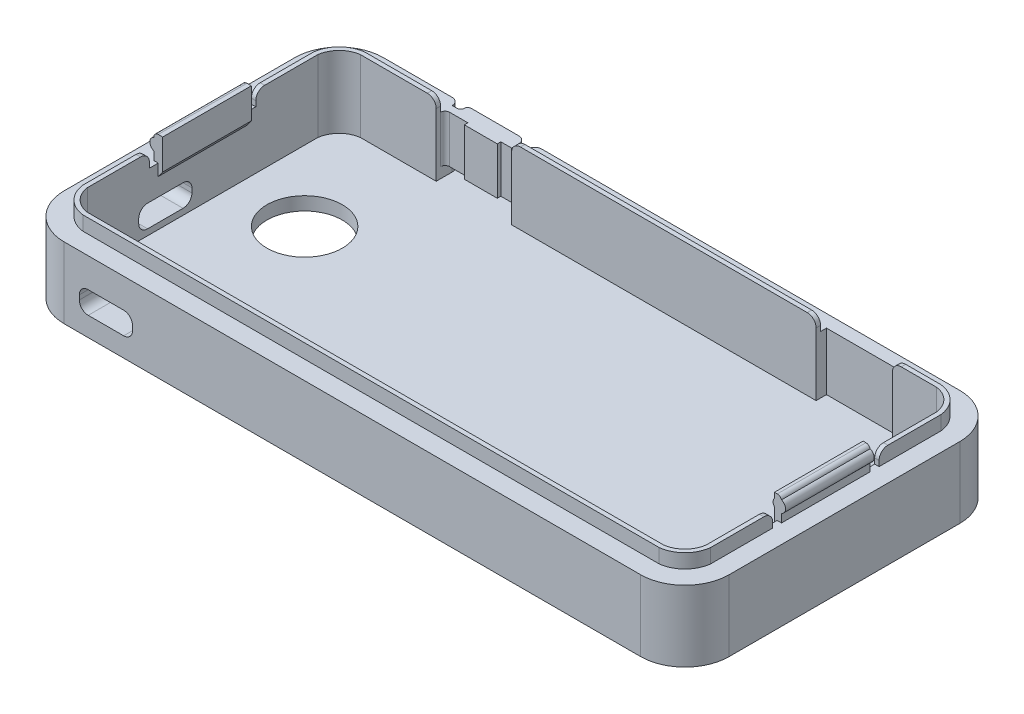
SolidWorks part; units mm, degrees
ref_plane "前视基准面" through (0, 0, 0) normal (0, 0, 1) x (1, 0, 0)
ref_plane "上视基准面" through (0, 0, 0) normal (0, 1, 0) x (1, 0, 0)
ref_plane "右视基准面" through (0, 0, 0) normal (1, 0, 0) x (0, 0, -1)
sketch "zero" plane through (0, 0, 0) normal (0, 1, 0) x (1, 0, 0)
  line L1 (-29.5, 15) -> (29.5, 15)
  line L2 (-32.5, 12) -> (-32.5, -12)
  line L3 (-29.5, -15) -> (29.5, -15)
  line L4 (32.5, 12) -> (32.5, -12)
  line L5 (-32.5, 15) -> (32.5, -15) construction
  line L6 (-32.5, -15) -> (32.5, 15) construction
  line L7 (-25.7, -15) -> (-14.5, -15)
  line L8 (-25.7, -15) -> (-25.7, -9.6569)
  line L9 (-25.7, -9.6569) -> (-14.5, -9.6569)
  line L10 (-14.5, -15) -> (-14.5, -9.6569)
  line L11 (5.2, -15) -> (12.7, -15)
  line L12 (5.2, -15) -> (5.2, -11)
  line L13 (5.2, -11) -> (12.7, -11)
  line L14 (12.7, -15) -> (12.7, -11)
  line L15 (17.8, -15) -> (25.3, -15)
  line L16 (17.8, -15) -> (17.8, -11)
  line L17 (17.8, -11) -> (25.3, -11)
  line L18 (25.3, -15) -> (25.3, -11)
  line L19 (-32.5, 7.7) -> (-19.5, 7.7)
  line L20 (-32.5, 7.7) -> (-32.5, -4.3)
  line L21 (-32.5, -4.3) -> (-19.5, -4.3)
  line L22 (-19.5, 7.7) -> (-19.5, -4.3)
  line L23 (-25.5, 14) -> (25.5, 14)
  line L24 (-25.5, 14) -> (-25.5, 8.8)
  line L25 (-25.5, 8.8) -> (25.5, 8.8)
  line L26 (25.5, 14) -> (25.5, 8.8)
  line L27 (-19.5, 7.2329) -> (-35.5, 7.2329)
  line L28 (-19.5, 7.2329) -> (-19.5, -3.7671)
  line L29 (-19.5, -3.7671) -> (-35.5, -3.7671)
  line L30 (-35.5, 7.2329) -> (-35.5, -3.7671)
  arc A0 (29.5, -15) -> (32.5, -12) centre (29.5, -12) ccw
  arc A1 (29.5, 15) -> (32.5, 12) centre (29.5, 12) cw
  arc A2 (-32.5, -12) -> (-29.5, -15) centre (-29.5, -12) ccw
  arc A3 (-29.5, 15) -> (-32.5, 12) centre (-29.5, 12) ccw
  circle A4 centre (-29, 11.4) radius 3
  circle A5 centre (-29, -11.5) radius 3
  circle A6 centre (29, 11.4) radius 3
  circle A7 centre (29, -11.5) radius 3
  circle A8 centre (-29, 11.4) radius 1.375
  circle A9 centre (-29, -11.5) radius 1.375
  circle A10 centre (29, -11.5) radius 1.375
  circle A11 centre (29, 11.4) radius 1.375
  point P0 (0, 0)
  dimension "D3" = 3
  dimension "D4" = 6
  dimension "D9" = 2.75
  dimension "D1" = 65
  dimension "D2" = 30
  dimension "D5" = 3.6
  dimension "D6" = 3.5
  dimension "D7" = 3.5
  dimension "D8" = 3.5
  dimension "D10" = 12
  dimension "D11" = 7.3
  dimension "D12" = 13
  dimension "D13" = 11.2
  dimension "D14" = 6.8
  dimension "D15" = 19.7
  dimension "D16" = 7.5
  dimension "D17" = 7.5
  dimension "D18" = 5.1
  dimension "D19" = 4
  dimension "D20" = 5.2
  dimension "D21" = 7
  dimension "D22" = 7
  dimension "D23" = 1
  dimension "D24" = 11
  dimension "D25" = 16
sketch "sugar" plane through (0, 0, 0) normal (0, 1, 0) x (1, 0, 0)
  line L1 (-29.5, 15) -> (29.5, 15)
  line L2 (-32.5, 12) -> (-32.5, -12)
  line L3 (-29.5, -15) -> (29.5, -15)
  line L4 (32.5, 12) -> (32.5, -12)
  line L5 (-32.5, 15) -> (32.5, -15) construction
  line L6 (-32.5, -15) -> (32.5, 15) construction
  line L7 (23.5, -11.5) -> (19.5, -11.5)
  line L8 (23.5, -11.5) -> (23.5, -13.9082)
  line L9 (23.5, -13.9082) -> (19.5, -13.9082)
  line L10 (19.5, -11.5) -> (19.5, -13.9082)
  line L11 (16, -11.0071) -> (8.5, -11.0071)
  line L12 (16, -11.0071) -> (16, -15)
  line L13 (16, -15) -> (8.5, -15)
  line L14 (8.5, -11.0071) -> (8.5, -15)
  line L15 (20.5, -13.9082) -> (22.5, -13.9082)
  line L16 (20.5, -13.9082) -> (20.5, -14.8173)
  line L17 (20.5, -14.8173) -> (22.5, -14.8173)
  line L18 (22.5, -13.9082) -> (22.5, -14.8173)
  arc A0 (29.5, 15) -> (32.5, 12) centre (29.5, 12) cw
  arc A1 (29.5, -15) -> (32.5, -12) centre (29.5, -12) ccw
  arc A2 (-32.5, -12) -> (-29.5, -15) centre (-29.5, -12) ccw
  arc A3 (-29.5, 15) -> (-32.5, 12) centre (-29.5, 12) ccw
  circle A4 centre (-29, 11.4) radius 3
  circle A5 centre (-29, 11.4) radius 1.375
  circle A6 centre (-29, -11.5) radius 3
  circle A7 centre (-29, -11.5) radius 1.375
  circle A8 centre (29, 11.4) radius 3
  circle A9 centre (29, 11.4) radius 1.375
  circle A10 centre (29, -11.5) radius 3
  circle A11 centre (29, -11.5) radius 1.375
  dimension "D3" = 3
  dimension "D1" = 65
  dimension "D2" = 30
  dimension "D4" = 9
  dimension "D5" = 4
  dimension "D6" = 3.5
  dimension "D7" = 7.5
  dimension "D8" = 2
  dimension "D9" = 1
sketch "case" plane through (0, 0, 0) normal (0, 1, 0) x (1, 0, 0)
  line L1 (-34.0422, 18) -> (30.9578, 18)
  line L2 (-39.0422, 13) -> (-39.0422, -13)
  line L3 (-34.0422, -18) -> (30.9578, -18)
  line L4 (35.9578, 13) -> (35.9578, -13)
  line L5 (-39.0422, 18) -> (35.9578, -18) construction
  line L6 (-39.0422, -18) -> (35.9578, 18) construction
  arc A0 (-39.0422, -13) -> (-34.0422, -18) centre (-34.0422, -13) ccw
  arc A1 (30.9578, -18) -> (35.9578, -13) centre (30.9578, -13) ccw
  arc A2 (30.9578, 18) -> (35.9578, 13) centre (30.9578, 13) cw
  arc A3 (-34.0422, 18) -> (-39.0422, 13) centre (-34.0422, 13) ccw
  point P0 (-1.5422, 0)
  point P3 (-1.5422, 0)
  dimension "D3" = 5
  dimension "D1" = 75
  dimension "D2" = 36
extrude "凸台-拉伸2" add sketch "case" along normal blind 8
sketch "草图2" plane through (0, 0, 0) normal (0, 1, 0) x (1, 0, 0)
  line L0 (-39.0422, 13) -> (-39.0422, -13) construction
  line L1 (-34.0422, -18) -> (30.9578, -18) construction
  line L2 (35.9578, -13) -> (35.9578, 13) construction
  line L3 (30.9578, 18) -> (-34.0422, 18) construction
  line L4 (-34.0422, -15.4) -> (30.9578, -15.4)
  line L5 (33.3578, -13) -> (33.3578, 13)
  line L6 (30.9578, 15.4) -> (-34.0422, 15.4)
  line L7 (-36.4422, 13) -> (-36.4422, -13)
  line L12 (33.8578, -13) -> (33.8578, 13)
  line L13 (30.9578, 15.9) -> (-34.0422, 15.9)
  line L14 (-36.9422, 13) -> (-36.9422, -13)
  line L15 (-34.0422, -15.9) -> (30.9578, -15.9)
  arc A4 (30.9578, -15.4) -> (33.3578, -13) centre (30.583, -12.6252) ccw
  arc A5 (33.3578, 13) -> (30.9578, 15.4) centre (30.583, 12.6252) ccw
  arc A6 (-34.0422, 15.4) -> (-36.4422, 13) centre (-33.6674, 12.6252) ccw
  arc A7 (-36.4422, -13) -> (-34.0422, -15.4) centre (-33.6674, -12.6252) ccw
  arc A12 (30.9578, -15.9) -> (33.8578, -13) centre (30.5796, -12.6217) ccw
  arc A13 (33.8578, 13) -> (30.9578, 15.9) centre (30.5796, 12.6217) ccw
  arc A14 (-34.0422, 15.9) -> (-36.9422, 13) centre (-33.6639, 12.6217) ccw
  arc A15 (-36.9422, -13) -> (-34.0422, -15.9) centre (-33.6639, -12.6217) ccw
  point P13 (0, 0)
  point P14 (30.9578, -15.9)
  point P15 (0, 0)
  point P16 (0, 0)
  point P17 (30.9578, -15.9)
  point P37 (0, 0)
  point P38 (0, 0)
  point P39 (0, 0)
  point P40 (0, 0)
  point P41 (0, 0)
  point P42 (0, 0)
  point P43 (0, 0)
  point P44 (0, 0)
  dimension "D6" = 2.1
  dimension "D2" = 2.6
  dimension "D3" = 2.6
  dimension "D4" = 2.6
  dimension "D5" = 2.6
  dimension "D1" = 2.1
  dimension "D7" = 2.1
  dimension "D8" = 2.1
ref_plane "基准面1" through (0, 8, 0) normal (0, 1, 0) x (1, 0, 0)
sketch "草图3" plane through (0, 8, 0) normal (0, 1, 0) x (1, 0, 0)
  line L4 (-34.0422, -15.4) -> (30.9578, -15.4)
  line L5 (33.3578, -13) -> (33.3578, 13)
  line L6 (30.9578, 15.4) -> (-34.0422, 15.4)
  line L7 (-36.4422, 13) -> (-36.4422, -13)
  line L8 (-34.0422, -15.4) -> (30.9578, -15.4)
  line L9 (33.3578, -13) -> (33.3578, 13)
  line L10 (30.9578, 15.4) -> (-34.0422, 15.4)
  line L11 (-36.4422, 13) -> (-36.4422, -13)
  line L12 (-36.9422, 13) -> (-36.9422, -13)
  line L13 (-34.0422, -15.9) -> (30.9578, -15.9)
  line L14 (33.8578, -13) -> (33.8578, 13)
  line L15 (30.9578, 15.9) -> (-34.0422, 15.9)
  line L16 (-36.9422, 13) -> (-36.9422, -13)
  line L17 (-34.0422, -15.9) -> (30.9578, -15.9)
  line L18 (33.8578, -13) -> (33.8578, 13)
  line L19 (30.9578, 15.9) -> (-34.0422, 15.9)
  arc A4 (30.9578, -15.4) -> (33.3578, -13) centre (30.583, -12.6252) ccw
  arc A5 (33.3578, 13) -> (30.9578, 15.4) centre (30.583, 12.6252) ccw
  arc A6 (-34.0422, 15.4) -> (-36.4422, 13) centre (-33.6674, 12.6252) ccw
  arc A7 (-36.4422, -13) -> (-34.0422, -15.4) centre (-33.6674, -12.6252) ccw
  arc A8 (30.9578, -15.4) -> (33.3578, -13) centre (30.583, -12.6252) ccw
  arc A9 (33.3578, 13) -> (30.9578, 15.4) centre (30.583, 12.6252) ccw
  arc A10 (-34.0422, 15.4) -> (-36.4422, 13) centre (-33.6674, 12.6252) ccw
  arc A11 (-36.4422, -13) -> (-34.0422, -15.4) centre (-33.6674, -12.6252) ccw
  arc A12 (-36.9422, -13) -> (-34.0422, -15.9) centre (-33.6639, -12.6217) ccw
  arc A13 (30.9578, -15.9) -> (33.8578, -13) centre (30.5796, -12.6217) ccw
  arc A14 (33.8578, 13) -> (30.9578, 15.9) centre (30.5796, 12.6217) ccw
  arc A15 (-34.0422, 15.9) -> (-36.9422, 13) centre (-33.6639, 12.6217) ccw
  arc A16 (-36.9422, -13) -> (-34.0422, -15.9) centre (-33.6639, -12.6217) ccw
  arc A17 (30.9578, -15.9) -> (33.8578, -13) centre (30.5796, -12.6217) ccw
  arc A18 (33.8578, 13) -> (30.9578, 15.9) centre (30.5796, 12.6217) ccw
  arc A19 (-34.0422, 15.9) -> (-36.9422, 13) centre (-33.6639, 12.6217) ccw
  dimension "D1" = 0
  dimension "D2" = 0
extrude "凸台-拉伸4" add sketch "草图3" along normal blind 1.6
sketch "草图5" plane through (0, 8, 0) normal (0, 1, 0) x (1, 0, 0)
  line L0 (33.3578, -13) -> (33.3578, 13) construction
  line L1 (33.0578, 5) -> (33.3578, 5)
  line L2 (33.0578, 5) -> (33.0578, -5)
  line L3 (33.0578, -5) -> (33.3578, -5)
  line L4 (33.3578, 5) -> (33.3578, -5)
  line L5 (33.0578, 5) -> (33.3578, -5) construction
  line L6 (33.0578, -5) -> (33.3578, 5) construction
  point P0 (33.2078, 0)
  dimension "D2" = 10
  dimension "D3" = 0.3
  dimension "D4" = 0
ref_plane "基准面3" through (33.8578, 0, 0) normal (1, 0, 0) x (0, 0, -1)
sketch "草图7" plane through (0, 8, 0) normal (0, 1, 0) x (1, 0, 0)
  line L0 (-36.9422, 13) -> (-36.9422, -13) construction
  line L1 (-36.9422, 5) -> (-36.4422, 5)
  line L2 (-36.9422, 5) -> (-36.9422, -5)
  line L3 (-36.9422, -5) -> (-36.4422, -5)
  line L4 (-36.4422, 5) -> (-36.4422, -5)
  line L5 (-36.4422, 13) -> (-36.4422, -13) construction
  point P10 (-36.4422, 0)
  dimension "D1" = 5
  dimension "D2" = 10
extrude "凸台-拉伸8" add sketch "草图7" along normal blind 2.8
ref_plane "基准面5" through (0, 0, 5) normal (0, 0, 1) x (1, 0, 0)
sketch "草图8" plane through (0, 0, 5) normal (0, 0, 1) x (1, 0, 0)
  line L0 (-34.0422, 8) -> (-39.0422, 8) construction
  line L1 (-36.9422, 10.8) -> (-36.9422, 9.6) construction
  circle A0 centre (-36.6922, 9.6) radius 0.7
  dimension "D1" = 1.4
  dimension "D2" = 1.6
  dimension "D3" = 0.25
extrude "凸台-拉伸9" add sketch "草图8" against normal blind 10
fillet "圆角1" radius 0.5 1 edges at (-36.9422, 10.8, 0)
ref_plane "基准面7" through (-36.9422, 0, 0) normal (-1, 0, 0) x (0, 0, 1)
sketch "草图11" plane through (-36.9422, 0, 0) normal (-1, 0, 0) x (0, 0, 1)
  line L0 (-13, 8) -> (13, 8) construction
  line L1 (5, 9.6) -> (6, 9.6)
  line L2 (5, 9.6) -> (5, 8)
  line L3 (5, 8) -> (6, 8)
  line L4 (6, 9.6) -> (6, 8)
  line L6 (-5, 9.6) -> (-6, 9.6)
  line L7 (-5, 9.6) -> (-5, 8)
  line L8 (-5, 8) -> (-6, 8)
  line L9 (-6, 9.6) -> (-6, 8)
  dimension "D1" = 1
  dimension "D2" = 1
extrude "切除-拉伸1" cut sketch "草图11" against normal blind 1.2
fillet "圆角2" radius 1 2 edges at (-36.6922, 9.6, 6) (-36.6922, 9.6, -6)
sketch "草图13" plane through (0, 8, 0) normal (0, 1, 0) x (1, 0, 0)
  line L1 (-36.4422, -5) -> (-35.9422, -5)
  line L2 (-36.4422, -5) -> (-36.4422, 5)
  line L3 (-36.4422, 5) -> (-35.9422, 5)
  line L4 (-35.9422, -5) -> (-35.9422, 5)
  dimension "D1" = 0.5
extrude "凸台-拉伸10" add sketch "草图13" along normal blind 2.8
sketch "草图14" plane through (0, 8, 0) normal (0, 1, 0) x (1, 0, 0)
  line L4 (-34.0422, -15.4) -> (30.9578, -15.4)
  line L5 (33.3578, -13) -> (33.3578, 13)
  line L6 (30.9578, 15.4) -> (-34.0422, 15.4)
  line L7 (-36.4422, 13) -> (-36.4422, -13)
  line L8 (-34.0422, -15.4) -> (30.9578, -15.4)
  line L9 (33.3578, -13) -> (33.3578, 13)
  line L10 (30.9578, 15.4) -> (-34.0422, 15.4)
  line L11 (-36.4422, 13) -> (-36.4422, -13)
  arc A4 (30.9578, -15.4) -> (33.3578, -13) centre (30.583, -12.6252) ccw
  arc A5 (33.3578, 13) -> (30.9578, 15.4) centre (30.583, 12.6252) ccw
  arc A6 (-34.0422, 15.4) -> (-36.4422, 13) centre (-33.6674, 12.6252) ccw
  arc A7 (-36.4422, -13) -> (-34.0422, -15.4) centre (-33.6674, -12.6252) ccw
  arc A8 (30.9578, -15.4) -> (33.3578, -13) centre (30.583, -12.6252) ccw
  arc A9 (33.3578, 13) -> (30.9578, 15.4) centre (30.583, 12.6252) ccw
  arc A10 (-34.0422, 15.4) -> (-36.4422, 13) centre (-33.6674, 12.6252) ccw
  arc A11 (-36.4422, -13) -> (-34.0422, -15.4) centre (-33.6674, -12.6252) ccw
  dimension "D1" = 0
extrude "切除-拉伸2" cut sketch "草图14" against normal blind 6.5
extrude "凸台-拉伸11" add sketch "草图13<2>" against normal blind 2
sketch "草图13<2>" plane through (0, 8, 0) normal (0, 1, 0) x (1, 0, 0) same geometry as "草图13"
extrude "凸台-拉伸12" add sketch "草图5" against normal blind 2 and the other way blind 1.6
sketch "草图17" plane through (0, 9.6, 0) normal (0, 1, 0) x (1, 0, 0)
  line L0 (33.3578, -13) -> (33.3578, -5) construction
  line L1 (33.3578, -5) -> (33.8578, -5)
  line L2 (33.3578, -5) -> (33.3578, -6)
  line L3 (33.3578, -6) -> (33.8578, -6)
  line L4 (33.8578, -5) -> (33.8578, -6)
  line L5 (33.3578, -13) -> (33.3578, 13) construction
  line L6 (33.8578, -13) -> (33.8578, 13) construction
  line L8 (33.3578, 5) -> (33.8578, 5)
  line L9 (33.3578, 5) -> (33.3578, 6)
  line L10 (33.3578, 6) -> (33.8578, 6)
  line L11 (33.8578, 5) -> (33.8578, 6)
  dimension "D1" = 1
  dimension "D2" = 1
extrude "切除-拉伸3" cut sketch "草图17" against normal blind 1.6
sketch "草图19" plane through (0, 9.6, 0) normal (0, 1, 0) x (1, 0, 0)
  line L0 (33.0578, 5) -> (33.0578, -5) construction
  line L1 (33.8578, -5) -> (33.0578, -5)
  line L2 (33.8578, -5) -> (33.8578, 5)
  line L3 (33.8578, 5) -> (33.0578, 5)
  line L4 (33.0578, -5) -> (33.0578, 5)
extrude "凸台-拉伸15" add sketch "草图19" along normal blind 1
sketch "草图20" plane through (0, 0, -5) normal (0, 0, -1) x (-1, 0, 0)
  line L0 (-30.9578, 8) -> (-35.9578, 8) construction
  line L3 (-33.8578, 8) -> (-33.8578, 10.6) construction
  circle A0 centre (-33.6078, 9.6) radius 0.7
  dimension "D1" = 1.4
  dimension "D2" = 1.6
  dimension "D3" = 0.25
extrude "凸台-拉伸16" add sketch "草图20" against normal blind 10
fillet "圆角4" radius 0.5 1 edges at (33.8578, 10.6, 0)
sketch "草图33" plane through (0, 1.5, 0) normal (0, 1, 0) x (1, 0, 0)
  line L3 (-39.0422, 13) -> (-39.0422, -13) construction
  line L4 (30.9578, 18) -> (-34.0422, 18) construction
  circle A0 centre (-28.5006, 3.5706) radius 4.25
  dimension "D1" = 8.5
  dimension "D2" = 10.5416
  dimension "D3" = 14.4294
chamfer "倒角11" distance 1 angle 54 1 edges at (-35.9422, 6, 0) first distance on face at (-36.1922, 6, 0)
fillet "圆角5" radius 1 2 edges at (33.6078, 9.6, 6) (33.6078, 9.6, -6)
extrude "切除-拉伸17" cut sketch "草图33" against normal up to next
sketch "草图44" plane through (0, 0, 0) normal (0, -1, 0) x (1, 0, 0)
  line B0 (-7.9307, 5.5082) -> (-8.7513, 5.9812)
  line B1 (-8.7513, 5.9812) -> (-13.0081, 8.4374)
  line B2 (-13.0081, 8.4374) -> (-13.8287, 8.9161)
  line B3 (-15.5497, 8.9161) -> (-16.3704, 8.4374)
  line B4 (-16.3704, 8.4374) -> (-20.6272, 5.9812)
  line B5 (-20.6272, 5.9812) -> (-21.4479, 5.5082)
  line B6 (-22.3084, 4.0209) -> (-22.3084, -2.7947)
  line B7 (-21.4479, -4.282) -> (-20.6272, -4.755)
  line B8 (-20.6272, -4.755) -> (-16.3704, -7.2112)
  line B9 (-16.3704, -7.2112) -> (-15.5497, -7.6898)
  line B10 (-13.8287, -7.6898) -> (-13.0081, -7.2112)
  line B11 (-13.0081, -7.2112) -> (-8.7513, -4.755)
  line B12 (-8.7513, -4.755) -> (-7.9307, -4.282)
  line B13 (-7.0702, -2.7947) -> (-7.0702, 4.0209)
  line B14 (-20.3537, 4.8301) -> (-15.0882, 7.8732)
  line B15 (-14.2846, 7.8732) -> (-9.0476, 4.8244)
  line B16 (-9.0419, 4.1235) -> (-14.1308, 1.0804)
  line B17 (-12.5522, -4.0769) -> (-13.1449, -4.4074)
  line B18 (-13.2019, -4.5043) -> (-13.2019, -6.2139)
  line B19 (-13.2588, -6.3108) -> (-14.3644, -6.9376)
  line B20 (-14.5297, -6.8407) -> (-14.5297, -1.5638)
  line B21 (-14.4727, -1.4669) -> (-12.5921, -0.4013)
  line B22 (-8.6487, -3.7236) -> (-9.7428, -4.3447)
  line B23 (-9.9081, -4.2479) -> (-9.9081, -1.7347)
  line B24 (-9.8511, -1.6379) -> (-8.757, -1.0224)
  line B25 (-8.5917, -1.1193) -> (-8.5917, -3.6267)
  line B26 (-12.6207, -3.0625) -> (-13.1449, -3.3247)
  line B27 (-13.2019, -3.205) -> (-13.2019, -1.8601)
  line B28 (-13.1449, -1.7632) -> (-12.6548, -1.4897)
  line B29 (-3.0754, 3.5422) -> (-4.9503, 3.5422)
  line B30 (-4.9503, 3.5422) -> (-4.9503, -3.0226)
  line B31 (-4.9503, -3.0226) -> (-4.1182, -3.0226)
  line B32 (-4.1182, -3.0226) -> (-4.1182, -0.4183)
  line B33 (-4.1182, -0.4183) -> (-3.0298, -0.4183)
  line B34 (-3.138, 0.2541) -> (-4.1182, 0.2541)
  line B35 (-4.1182, 0.2541) -> (-4.1182, 2.8698)
  line B36 (-4.1182, 2.8698) -> (-3.1722, 2.8698)
  line B37 (0.4634, 1.844) -> (0.4634, -3.0226)
  line B38 (0.4634, -3.0226) -> (1.2784, -3.0226)
  line B39 (1.2784, -3.0226) -> (1.2784, 1.844)
  line B40 (1.2784, 1.844) -> (0.4634, 1.844)
  line B41 (5.9855, 0.767) -> (5.1535, 1.0975)
  line B42 (6.3103, 1.8839) -> (7.1081, 2.8869)
  line B43 (3.877, -0.0764) -> (4.7261, -0.4355)
  line B44 (3.176, -1.0851) -> (2.27, -2.1906)
  line B45 (11.0915, 2.072) -> (11.0915, -1.2675)
  line B46 (9.6497, -0.8799) -> (9.6497, 2.072)
  line B47 (9.6497, 2.072) -> (8.0598, 2.072)
  line B48 (8.0598, 2.072) -> (8.0598, -1.0794)
  line B49 (11.2738, -2.3217) -> (11.3878, -3.0226)
  line B50 (11.3878, -3.0226) -> (12.6871, -3.0226)
  line B51 (12.6871, -3.0226) -> (12.6871, 2.072)
  line B52 (12.6871, 2.072) -> (11.0915, 2.072)
  line B53 (16.5394, -2.0197) -> (15.7359, -2.0197)
  line B54 (17.6335, 0.9208) -> (18.4199, 0.9208)
  line B55 (18.4199, 0.9208) -> (18.4199, 2.072)
  line B56 (18.4199, 2.072) -> (16.5508, 2.072)
  line B57 (15.753, -3.2392) -> (16.2374, -3.2392)
  line B58 (18.8758, 1.5306) -> (19.4343, 0.482)
  line B59 (21.6796, -2.5098) -> (21.8334, -3.0226)
  line B60 (21.8334, -3.0226) -> (23.1327, -3.0226)
  line B61 (23.1327, -3.0226) -> (23.1327, -0.1277)
  line B62 (21.5371, -0.6919) -> (21.5371, -1.5068)
  line B63 (25.6231, 1.1887) -> (25.4806, 2.072)
  line B64 (25.4806, 2.072) -> (24.1813, 2.072)
  line B65 (24.1813, 2.072) -> (24.1813, -3.0226)
  line B66 (24.1813, -3.0226) -> (25.7655, -3.0226)
  line B67 (25.7655, -3.0226) -> (25.7655, -0.1106)
  line B68 (27.4238, 0.7214) -> (27.6916, 2.0948)
  line B69 (-13.1449, -3.3247) -> (-13.1449, -4.4074)
  line B70 (-13.2019, -3.205) -> (-13.2019, -4.5043)
  spline B71 degree 3 poles (-13.8287, 8.9161) (-14.0966, 9.0642) (-14.3929, 9.144) (-14.6892, 9.144) knots 3 3 3 3 4 4 4 4
  spline B72 degree 3 poles (-14.6892, 9.144) (-14.9856, 9.144) (-15.2819, 9.0642) (-15.5497, 8.9161) knots 4 4 4 4 5 5 5 5
  spline B73 degree 3 poles (-21.4479, 5.5082) (-21.9778, 5.2005) (-22.3084, 4.6307) (-22.3084, 4.0209) knots 8 8 8 8 9 9 9 9
  spline B74 degree 3 poles (-22.3084, -2.7947) (-22.3084, -3.4101) (-21.9778, -3.9743) (-21.4479, -4.282) knots 10 10 10 10 11 11 11 11
  spline B75 degree 3 poles (-15.5497, -7.6898) (-15.2819, -7.8437) (-14.9856, -7.9178) (-14.6892, -7.9178) knots 14 14 14 14 15 15 15 15
  spline B76 degree 3 poles (-14.6892, -7.9178) (-14.3929, -7.9178) (-14.0966, -7.8437) (-13.8287, -7.6898) knots 15 15 15 15 16 16 16 16
  spline B77 degree 3 poles (-7.9307, -4.282) (-7.395, -3.9743) (-7.0702, -3.4101) (-7.0702, -2.7947) knots 19 19 19 19 20 20 20 20
  spline B78 degree 3 poles (-7.0702, 4.0209) (-7.0702, 4.6307) (-7.395, 5.2005) (-7.9307, 5.5082) knots 21 21 21 21 22 22 22 22
  spline B79 degree 2 poles (-15.242, 1.0804) (-20.3936, 4.0551) (-20.405, 4.0608) knots 0 0 0 1 1 1
  spline B80 degree 3 poles (-20.405, 4.0608) (-20.6728, 4.2545) (-20.6443, 4.6649) (-20.3537, 4.8301) knots 1 1 1 1 2 2 2 2
  spline B81 degree 3 poles (-15.0882, 7.8732) (-14.8431, 8.0157) (-14.5353, 8.0157) (-14.2846, 7.8732) knots 3 3 3 3 4 4 4 4
  spline B82 degree 3 poles (-9.0476, 4.8244) (-8.7798, 4.6706) (-8.7741, 4.2831) (-9.0419, 4.1235) knots 5 5 5 5 6 6 6 6
  spline B83 degree 3 poles (-14.1308, 1.0804) (-14.4727, 0.8809) (-14.9001, 0.8809) (-15.242, 1.0804) knots 7 7 7 7 8 8 8 8
  spline B84 degree 3 poles (-13.2019, -6.2139) (-13.2019, -6.2538) (-13.219, -6.288) (-13.2588, -6.3108) knots 3 3 3 3 4 4 4 4
  spline B85 degree 3 poles (-14.3644, -6.9376) (-14.4385, -6.9775) (-14.5297, -6.9262) (-14.5297, -6.8407) knots 5 5 5 5 6 6 6 6
  spline B86 degree 3 poles (-14.5297, -1.5638) (-14.5297, -1.5239) (-14.5126, -1.484) (-14.4727, -1.4669) knots 7 7 7 7 8 8 8 8
  spline B87 degree 3 poles (-12.5921, -0.4013) (-11.3726, 0.2883) (-10.364, 0.4251) (-10.364, -0.9426) knots 9 9 9 9 10 10 10 10
  spline B88 degree 3 poles (-10.364, -0.9426) (-10.364, -2.259) (-11.384, -3.4158) (-12.5522, -4.0769) knots 10 10 10 10 11 11 11 11
  spline B89 degree 3 poles (-8.5917, -3.6267) (-8.5917, -3.6666) (-8.6145, -3.7065) (-8.6487, -3.7236) knots 0 0 0 0 1 1 1 1
  spline B90 degree 3 poles (-9.7428, -4.3447) (-9.8169, -4.3846) (-9.9081, -4.3333) (-9.9081, -4.2479) knots 2 2 2 2 3 3 3 3
  spline B91 degree 3 poles (-9.9081, -1.7347) (-9.9081, -1.6949) (-9.8853, -1.6606) (-9.8511, -1.6379) knots 4 4 4 4 5 5 5 5
  spline B92 degree 3 poles (-8.757, -1.0224) (-8.6829, -0.9825) (-8.5917, -1.0338) (-8.5917, -1.1193) knots 6 6 6 6 7 7 7 7
  spline B93 degree 3 poles (-9.247, 0.6473) (-8.8082, 0.898) (-8.4948, 0.7898) (-8.4948, 0.3909) (-8.4948, -0.0023) (-8.8082, -0.4639) (-9.247, -0.709) knots 2 2 2 2 3 3 3 4 4 4 4
  spline B94 degree 3 poles (-9.247, -0.709) (-9.6915, -0.9654) (-10.0049, -0.8571) (-10.0049, -0.4639) (-10.0049, -0.0593) (-9.6915, 0.3966) (-9.247, 0.6473) knots 0 0 0 0 1 1 1 2 2 2 2
  spline B95 degree 3 poles (-11.6633, -1.6778) (-11.6633, -2.2191) (-11.9709, -2.6978) (-12.6207, -3.0625) knots 0 0 0 0 1 1 1 1
  spline B96 degree 3 poles (-13.2019, -1.8601) (-13.2019, -1.8202) (-13.1791, -1.7803) (-13.1449, -1.7632) knots 4 4 4 4 5 5 5 5
  spline B97 degree 3 poles (-12.6548, -1.4897) (-12.0166, -1.125) (-11.6633, -1.1193) (-11.6633, -1.6778) knots 6 6 6 6 7 7 7 7
  spline B98 degree 3 poles (-3.0298, -0.4183) (-1.5994, -0.4183) (-0.6136, 0.2313) (-0.6136, 1.6161) knots 5 5 5 5 6 6 6 6
  spline B99 degree 3 poles (-0.6136, 1.6161) (-0.6136, 3.0521) (-1.5994, 3.5422) (-3.0754, 3.5422) knots 6 6 6 6 7 7 7 7
  spline B100 degree 3 poles (-3.1722, 2.8698) (-2.0211, 2.8698) (-1.4398, 2.5678) (-1.4398, 1.6161) knots 3 3 3 3 4 4 4 4
  spline B101 degree 3 poles (-1.4398, 1.6161) (-1.4398, 0.6758) (-1.9813, 0.2541) (-3.138, 0.2541) knots 4 4 4 4 5 5 5 5
  spline B102 degree 3 poles (0.8738, 2.847) (1.1986, 2.847) (1.4379, 3.0692) (1.4379, 3.3712) (1.4379, 3.7075) (1.1986, 3.9012) (0.8738, 3.9012) knots 2 2 2 2 3 3 3 4 4 4 4
  spline B103 degree 3 poles (0.8738, 3.9012) (0.549, 3.9012) (0.3096, 3.7075) (0.3096, 3.3712) (0.3096, 3.0692) (0.549, 2.847) (0.8738, 2.847) knots 0 0 0 0 1 1 1 2 2 2 2
  spline B104 degree 3 poles (5.1535, 1.0975) (4.5665, 1.3312) (4.1448, 1.4736) (4.1448, 1.844) knots 1 1 1 1 2 2 2 2
  spline B105 degree 3 poles (4.1448, 1.844) (4.1448, 2.1973) (4.4469, 2.3968) (4.9426, 2.3968) knots 2 2 2 2 3 3 3 3
  spline B106 degree 3 poles (4.9426, 2.3968) (5.4612, 2.3968) (5.8715, 2.2201) (6.3103, 1.8839) knots 3 3 3 3 4 4 4 4
  spline B107 degree 3 poles (7.1081, 2.8869) (6.5269, 3.4738) (5.7119, 3.7702) (4.9426, 3.7702) knots 5 5 5 5 6 6 6 6
  spline B108 degree 3 poles (4.9426, 3.7702) (3.5237, 3.7702) (2.5207, 2.8698) (2.5207, 1.7528) knots 6 6 6 6 7 7 7 7
  spline B109 degree 3 poles (2.5207, 1.7528) (2.5207, 0.7841) (3.176, 0.2028) (3.877, -0.0764) knots 7 7 7 7 8 8 8 8
  spline B110 degree 3 poles (4.7261, -0.4355) (5.2959, -0.6748) (5.6664, -0.8002) (5.6664, -1.1877) knots 9 9 9 9 10 10 10 10
  spline B111 degree 3 poles (5.6664, -1.1877) (5.6664, -1.5467) (5.3871, -1.7689) (4.7945, -1.7689) knots 10 10 10 10 11 11 11 11
  spline B112 degree 3 poles (4.7945, -1.7689) (4.2702, -1.7689) (3.649, -1.4897) (3.176, -1.0851) knots 11 11 11 11 12 12 12 12
  spline B113 degree 3 poles (2.27, -2.1906) (2.9595, -2.8232) (3.894, -3.148) (4.7602, -3.148) knots 13 13 13 13 14 14 14 14
  spline B114 degree 3 poles (4.7602, -3.148) (6.373, -3.148) (7.3075, -2.1735) (7.3075, -1.0623) knots 14 14 14 14 15 15 15 15
  spline B115 degree 3 poles (7.3075, -1.0623) (7.3075, -0.122) (6.8118, 0.4365) (5.9855, 0.767) knots 15 15 15 15 16 16 16 16
  spline B116 degree 3 poles (11.0915, -1.2675) (10.8237, -1.6436) (10.6014, -1.786) (10.2424, -1.786) knots 1 1 1 1 2 2 2 2
  spline B117 degree 3 poles (10.2424, -1.786) (9.8378, -1.786) (9.6497, -1.5866) (9.6497, -0.8799) knots 2 2 2 2 3 3 3 3
  spline B118 degree 3 poles (8.0598, -1.0794) (8.0749, -2.3501) (8.5574, -3.1422) (9.6685, -3.129) knots 6 6 6 6 7 7 7 7
  spline B119 degree 3 poles (9.6685, -3.129) (10.3637, -3.1373) (10.8462, -2.8182) (11.2738, -2.3217) knots 7 7 7 7 8 8 8 8
  spline B120 degree 3 poles (15.7359, -2.0197) (15.1888, -2.0197) (14.9837, -1.9114) (14.9837, -1.6778) knots 1 1 1 1 2 2 2 2
  spline B121 degree 3 poles (14.9837, -1.6778) (14.9837, -1.5068) (15.0235, -1.427) (15.1432, -1.3187) knots 2 2 2 2 3 3 3 3
  spline B122 degree 3 poles (15.1432, -1.3187) (15.3655, -1.3814) (15.5706, -1.4099) (15.7416, -1.4099) knots 3 3 3 3 4 4 4 4
  spline B123 degree 3 poles (15.7416, -1.4099) (16.8699, -1.4099) (17.776, -0.8913) (17.776, 0.2997) knots 4 4 4 4 5 5 5 5
  spline B124 degree 3 poles (17.776, 0.2997) (17.776, 0.5447) (17.7133, 0.7784) (17.6335, 0.9208) knots 5 5 5 5 6 6 6 6
  spline B125 degree 3 poles (16.5508, 2.072) (16.3171, 2.1574) (16.0379, 2.1973) (15.7416, 2.1973) knots 9 9 9 9 10 10 10 10
  spline B126 degree 3 poles (15.7416, 2.1973) (14.6418, 2.1845) (13.6174, 1.5685) (13.632, 0.3206) knots 10 10 10 10 11 11 11 11
  spline B127 degree 3 poles (13.632, 0.3206) (13.6188, -0.2719) (13.9388, -0.7521) (14.2921, -1.0108) knots 11 11 11 11 12 12 12 12
  spline B128 degree 3 poles (14.2921, -1.0108) (13.9616, -1.2444) (13.7279, -1.6035) (13.7279, -1.9625) knots 13 13 13 13 14 14 14 14
  spline B129 degree 3 poles (13.7279, -1.9625) (13.7279, -2.3899) (13.9274, -2.6577) (14.1952, -2.8401) knots 14 14 14 14 15 15 15 15
  spline B130 degree 3 poles (14.1952, -2.8401) (13.7276, -3.0899) (13.4846, -3.4373) (13.4939, -3.8589) knots 16 16 16 16 17 17 17 17
  spline B131 degree 3 poles (13.4939, -3.8589) (13.4836, -4.7706) (14.4423, -5.152) (15.6162, -5.1653) knots 17 17 17 17 18 18 18 18
  spline B132 degree 3 poles (15.6162, -5.1653) (17.3885, -5.1653) (18.4998, -4.4017) (18.4998, -3.3247) knots 18 18 18 18 19 19 19 19
  spline B133 degree 3 poles (18.4998, -3.3247) (18.4998, -2.4015) (17.7931, -2.0197) (16.5394, -2.0197) knots 19 19 19 19 20 20 20 20
  spline B134 degree 3 poles (15.7416, -0.4525) (15.3769, -0.4525) (15.0977, -0.1847) (15.0977, 0.3453) (15.0977, 0.8639) (15.3769, 1.1317) (15.7416, 1.1317) knots 2 2 2 2 3 3 3 4 4 4 4
  spline B135 degree 3 poles (15.7416, 1.1317) (16.1177, 1.1317) (16.3855, 0.8639) (16.3855, 0.3453) (16.3855, -0.1847) (16.1177, -0.4525) (15.7416, -0.4525) knots 0 0 0 0 1 1 1 2 2 2 2
  spline B136 degree 3 poles (15.8669, -4.1681) (15.2116, -4.1681) (14.7842, -3.9914) (14.7842, -3.6324) knots 0 0 0 0 1 1 1 1
  spline B137 degree 3 poles (14.7842, -3.6324) (14.7842, -3.4614) (14.8639, -3.319) (15.0235, -3.1765) knots 1 1 1 1 2 2 2 2
  spline B138 degree 3 poles (15.0235, -3.1765) (15.1888, -3.2221) (15.3826, -3.2392) (15.753, -3.2392) knots 2 2 2 2 3 3 3 3
  spline B139 degree 3 poles (16.2374, -3.2392) (16.7103, -3.2392) (16.9782, -3.3019) (16.9782, -3.6039) knots 4 4 4 4 5 5 5 5
  spline B140 degree 3 poles (16.9782, -3.6039) (16.9782, -3.9287) (16.5223, -4.1681) (15.8669, -4.1681) knots 5 5 5 5 6 6 6 6
  spline B141 degree 3 poles (21.0699, 2.1973) (20.2777, 2.1973) (19.5483, 1.9295) (18.8758, 1.5306) knots 0 0 0 0 1 1 1 1
  spline B142 degree 3 poles (19.4343, 0.482) (19.9415, 0.767) (20.3632, 0.9265) (20.7678, 0.9265) knots 2 2 2 2 3 3 3 3
  spline B143 degree 3 poles (20.7678, 0.9265) (21.2863, 0.9265) (21.503, 0.6872) (21.5371, 0.2769) knots 3 3 3 3 4 4 4 4
  spline B144 degree 3 poles (21.5371, 0.2769) (19.5483, 0.0603) (18.7048, -0.5209) (18.7048, -1.598) knots 4 4 4 4 5 5 5 5
  spline B145 degree 3 poles (18.7048, -1.598) (18.7048, -2.4471) (19.2804, -3.148) (20.2208, -3.148) knots 5 5 5 5 6 6 6 6
  spline B146 degree 3 poles (20.2208, -3.148) (20.7849, -3.148) (21.2579, -2.8859) (21.6796, -2.5098) knots 6 6 6 6 7 7 7 7
  spline B147 degree 3 poles (23.1327, -0.1277) (23.1327, 1.4679) (22.3862, 2.1973) (21.0699, 2.1973) knots 11 11 11 11 12 12 12 12
  spline B148 degree 3 poles (21.5371, -1.5068) (21.3034, -1.7575) (21.0926, -1.9114) (20.7678, -1.9114) knots 0 0 0 0 1 1 1 1
  spline B149 degree 3 poles (20.7678, -1.9114) (20.4372, -1.9114) (20.2208, -1.7689) (20.2208, -1.4726) knots 1 1 1 1 2 2 2 2
  spline B150 degree 3 poles (20.2208, -1.4726) (20.2208, -1.1136) (20.5456, -0.8287) (21.5371, -0.6919) knots 2 2 2 2 3 3 3 3
  spline B151 degree 3 poles (27.0762, 2.1973) (26.5633, 2.1973) (25.9991, 1.8668) (25.6231, 1.1887) knots 0 0 0 0 1 1 1 1
  spline B152 degree 3 poles (25.7655, -0.1106) (26.0334, 0.5618) (26.4893, 0.8011) (26.8653, 0.8011) knots 7 7 7 7 8 8 8 8
  spline B153 degree 3 poles (26.8653, 0.8011) (27.0933, 0.8011) (27.2415, 0.767) (27.4238, 0.7214) knots 8 8 8 8 9 9 9 9
  spline B154 degree 3 poles (27.6916, 2.0948) (27.5492, 2.1574) (27.3782, 2.1973) (27.0762, 2.1973) knots 10 10 10 10 11 11 11 11
sketch_block_instance "块2-1"
sketch_block "块2"
extrude "切除-拉伸19" cut sketch "草图44" against normal blind 0.5
sketch "草图45" plane through (0, 0, 18) normal (0, 0, 1) x (1, 0, 0)
  line L0 (-39.0422, 0) -> (-34.0422, 0) construction
  line L1 (-26.3406, 2.1843) -> (-32.3406, 2.1843)
  line L2 (-26.3406, 2.1843) -> (-26.3406, 4.6843)
  line L3 (-26.3406, 4.6843) -> (-32.3406, 4.6843)
  line L4 (-32.3406, 2.1843) -> (-32.3406, 4.6843)
  line L5 (-39.0422, 8) -> (-39.0422, 0) construction
  dimension "D1" = 6
  dimension "D2" = 2.5
  dimension "D3" = 2.1843
  dimension "D4" = 6.7016
extrude "切除-拉伸20" cut sketch "草图45" against normal up to next
fillet "圆角12" radius 1 4 edges at (-32.3406, 2.1843, 16.7) (-32.3406, 4.6843, 16.7) (-26.3406, 2.1843, 16.7) (-26.3406, 4.6843, 16.7)
sketch "草图46" plane through (0, 9.6, 0) normal (0, 1, 0) x (1, 0, 0)
  line L0 (-39.0422, 13) -> (-39.0422, -13) construction
  line L1 (-25.4906, 15.4) -> (-16.9906, 15.4)
  line L2 (-25.4906, 15.4) -> (-25.4906, 16.4)
  line L3 (-25.4906, 16.4) -> (-16.9906, 16.4)
  line L4 (-16.9906, 15.4) -> (-16.9906, 16.4)
  line L5 (35.9578, -13) -> (35.9578, 13) construction
  line L6 (17.3578, 15.3706) -> (25.9578, 15.3706)
  line L7 (17.3578, 15.3706) -> (17.3578, 16.5706)
  line L8 (17.3578, 16.5706) -> (25.9578, 16.5706)
  line L9 (25.9578, 15.3706) -> (25.9578, 16.5706)
  line L10 (30.9578, 15.4) -> (-34.0422, 15.4) construction
  point P12 (0, 0)
  dimension "D1" = 1
  dimension "D2" = 8.5
  dimension "D3" = 13.5516
  dimension "D4" = 1.2
  dimension "D5" = 8.6
  dimension "D6" = 10
extrude "切除-拉伸21" cut sketch "草图46" against normal up to surface (8.1 mm away) up to face at (-28.5006, 1.5, 0.6794)
fillet "圆角13" radius 1 4 edges at (17.3578, 9.6, -15.65) (25.9578, 9.6, -15.65) (-25.4906, 9.6, -15.65) (-16.9906, 9.6, -15.65)
sketch "草图49" plane through (0, 0, -18) normal (0, 0, -1) x (-1, 0, 0)
  line L0 (25.4906, 2.6843) -> (24.5368, 2.6843)
  line L1 (25.4906, 1.5) -> (25.4906, 8) construction
  line L3 (24.5368, 2.6843) -> (17.983, 2.6843)
  line L4 (17.983, 2.6843) -> (17.983, 8)
  line L5 (-30.9578, 8) -> (34.0422, 8) construction
  line L6 (17.983, 8) -> (16.9906, 8)
  line L7 (16.9906, 1.5) -> (16.9906, 8) construction
  line L8 (16.9906, 8) -> (16.9906, 1.5)
  line L10 (16.9906, 1.5) -> (25.4906, 1.5)
  line L11 (25.4906, 1.5) -> (34.0422, 1.5) construction
  line L12 (25.4906, 1.5) -> (25.4906, 2.6843)
  point P4 (0, 0)
  point P5 (0, 0)
  point P14 (0, 0)
  point P15 (0, 0)
  point P19 (0, 0)
  point P20 (0, 0)
  point P21 (0, 0)
  point P22 (0, 0)
extrude "切除-拉伸22" cut sketch "草图49" against normal up to next
sketch "草图51" plane through (0, 0, -18) normal (0, 0, -1) x (-1, 0, 0)
  line L0 (17.983, 8) -> (34.0422, 8) construction
  line L1 (24.5368, 2.6843) -> (25.4906, 2.6843)
  line L2 (24.5368, 2.6843) -> (24.5368, 8)
  line L3 (24.5368, 8) -> (25.4906, 8)
  line L4 (25.4906, 2.6843) -> (25.4906, 8)
  line L5 (25.4906, 2.6843) -> (25.4906, 8) construction
  point P8 (0, 0)
extrude "切除-拉伸23" cut sketch "草图51" against normal blind 0.8
fillet "圆角14" radius 0.8 3 edges at (-17.983, 5.3422, -18) (-25.4906, 4.75, -18) (-16.9906, 4.75, -18)
sketch "草图52" plane through (0, 0, -16.4) normal (0, 0, 1) x (1, 0, 0)
  line L0 (-24.5368, 2.6843) -> (-18.783, 2.6843) construction
  line L1 (-22.9229, 8) -> (-19.201, 8)
  line L2 (-22.9229, 8) -> (-22.9229, 2.6843)
  line L3 (-22.9229, 2.6843) -> (-19.201, 2.6843)
  line L4 (-19.201, 8) -> (-19.201, 2.6843)
  line L5 (-18.783, 8) -> (-24.5368, 8) construction
  point P4 (0, 0)
  point P7 (0, 0)
extrude "凸台-拉伸18" add sketch "草图52" along normal blind 0.4
fillet "圆角15" radius 0.5 1 edges at (-25.4906, 5.3422, -16.4)
sketch "草图53" plane through (-39.0422, 0, 0) normal (-1, 0, 0) x (0, 0, 1)
  line L1 (7.2, 2.1843) -> (1.2, 2.1843)
  line L2 (7.2, 2.1843) -> (7.2, 4.6843)
  line L3 (7.2, 4.6843) -> (1.2, 4.6843)
  line L4 (1.2, 2.1843) -> (1.2, 4.6843)
  line L5 (18, 8) -> (18, 0) construction
  dimension "D1" = 6
  dimension "D3" = 10.8
extrude "切除-拉伸24" cut sketch "草图53" against normal up to next
fillet "圆角16" radius 1 4 edges at (-37.7422, 4.6843, 7.2) (-37.7422, 4.6843, 1.2) (-37.7422, 2.1843, 1.2) (-37.7422, 2.1843, 7.2)
fillet "圆角17" radius 0.4 2 edges at (-24.5368, 5.3422, -18) (-24.5368, 5.3422, -17.2)
